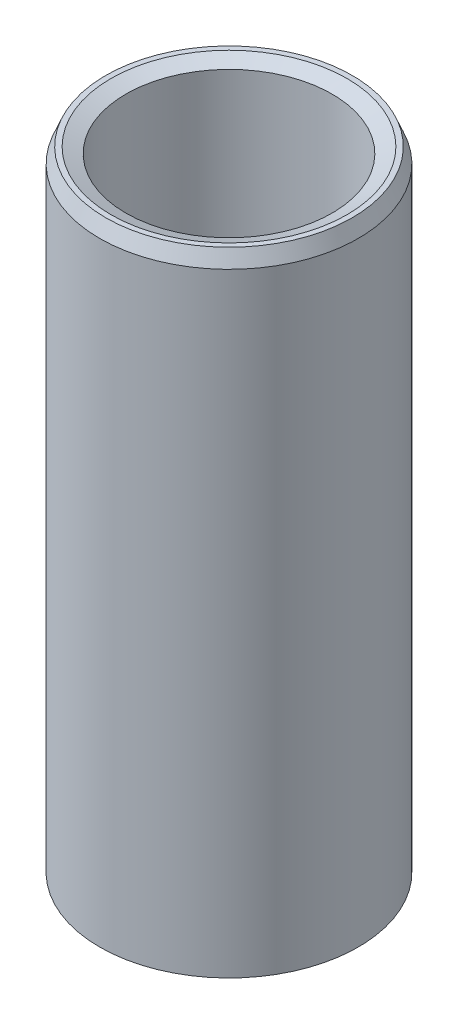
SolidWorks part; units mm, degrees
ref_plane "Front Plane" through (0, 0, 0) normal (0, 0, 1) x (1, 0, 0)
ref_plane "Top Plane" through (0, 0, 0) normal (0, 1, 0) x (1, 0, 0)
ref_plane "Right Plane" through (0, 0, 0) normal (1, 0, 0) x (0, 0, -1)
sketch "Sketch1" plane through (0, 0, 0) normal (0, 1, 0) x (1, 0, 0)
  circle A0 centre (0, 0) radius 30
  dimension "SLEEVE_OD" = 60
extrude "Boss-Extrude1" add sketch "Sketch1" along normal blind 147.2114
sketch "Sketch2" plane through (0, 0, 0) normal (0, 1, 0) x (1, 0, 0)
  circle A0 centre (0, 0) radius 23.9258
  dimension "BORE_D" = 47.8516
extrude "Cut-Extrude1" cut sketch "Sketch2" along normal through all
chamfer "Chamfer1" distance 3.4512 angle 22.136 4 edges at (0, 147.2114, 23.9258) (0, 0, 23.9258) (0, 0, 30) (0, 147.2114, 30) first distance on face at (0, 147.2114, 23.9258) first distance on face at (0, 0, 23.9258) first distance on face at (0, 147.2114, 30)
